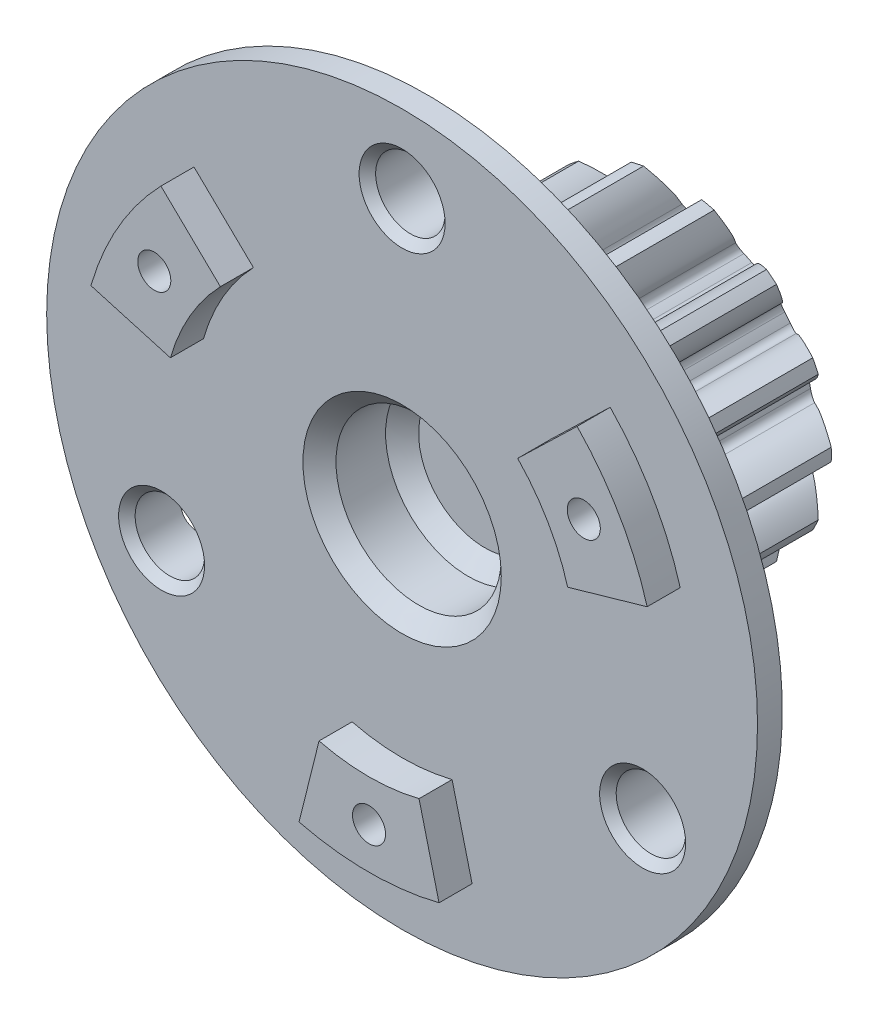
SolidWorks part; units mm, degrees
ref_plane "Front Plane" through (0, 0, 0) normal (0, 0, 1) x (1, 0, 0)
ref_plane "Top Plane" through (0, 0, 0) normal (0, 1, 0) x (1, 0, 0)
ref_plane "Right Plane" through (0, 0, 0) normal (1, 0, 0) x (0, 0, -1)
ref_axis "Axis1" through (0, 0, -88.99) along (0, 0, 1)
sketch "Sketch1" plane through (0, 0, 0) normal (0, 0, 1) x (1, 0, 0)
  circle A0 centre (0, 0) radius 9.6
extrude "LaShenA" add sketch "Sketch1" along normal blind 15
sketch "SketchA" plane through (0, 0, 15) normal (0, 0, 1) x (1, 0, 0)
  line L0 (0, 0) -> (0, 9.6) construction
  arc A0 (0.2639, 6.895) -> (-0.2639, 6.895) centre (0, 0) ccw
  arc A1 (2.4844, 10.0489) -> (-2.4844, 10.0489) centre (0, 0) ccw
  arc A2 (-0.2639, 6.895) -> (-0.7348, 7.3025) centre (-0.2814, 7.3506) cw
  arc A3 (0.7348, 7.3025) -> (0.2639, 6.895) centre (0.2814, 7.3506) cw
  circle A4 centre (0, 0) radius 7.8934 construction
  circle A5 centre (0, 0) radius 9.6 construction
  circle A6 centre (0, 0) radius 6.9 construction
  circle A7 centre (0, 0) radius 8.4 construction
  spline S0 degree 3 poles (0.7348, 7.3025) (0.7544, 7.4871) (0.7376, 7.7039) (0.7817, 7.9284) (0.7974, 7.9855) (0.8111, 8.0306) (0.8285, 8.0821) (0.85, 8.1398) (0.8759, 8.2036) (0.9067, 8.2732) (0.9427, 8.3484) (0.9843, 8.4289) (1.0318, 8.5144) (1.0856, 8.6047) (1.146, 8.6994) (1.2133, 8.7982) (1.2878, 8.9008) (1.3699, 9.0069) (1.4597, 9.116) (1.5576, 9.2278) (1.6637, 9.3419) (1.7784, 9.4579) (1.9017, 9.5753) (2.034, 9.6938) (2.2261, 9.8557) (2.3786, 9.9726) (2.4844, 10.0489) knots 0.117633 0.117633 0.117633 0.117633 0.26174 0.285267 0.295626 0.307868 0.321993 0.338001 0.355893 0.375668 0.397327 0.420869 0.446294 0.473603 0.502795 0.53387 0.566829 0.601671 0.638396 0.677005 0.717497 0.759872 0.804131 0.850273 0.898299 1 1 1 1
  spline S1 degree 3 poles (-0.7348, 7.3025) (-0.7544, 7.4871) (-0.7376, 7.7039) (-0.7817, 7.9284) (-0.7974, 7.9855) (-0.8111, 8.0306) (-0.8285, 8.0821) (-0.85, 8.1398) (-0.8759, 8.2036) (-0.9067, 8.2732) (-0.9427, 8.3484) (-0.9843, 8.4289) (-1.0318, 8.5144) (-1.0856, 8.6047) (-1.146, 8.6994) (-1.2133, 8.7982) (-1.2878, 8.9008) (-1.3699, 9.0069) (-1.4597, 9.116) (-1.5576, 9.2278) (-1.6637, 9.3419) (-1.7784, 9.4579) (-1.9017, 9.5753) (-2.034, 9.6938) (-2.2261, 9.8557) (-2.3786, 9.9726) (-2.4844, 10.0489) knots 0.117633 0.117633 0.117633 0.117633 0.26174 0.285267 0.295626 0.307868 0.321993 0.338001 0.355893 0.375668 0.397327 0.420869 0.446294 0.473603 0.502795 0.53387 0.566829 0.601671 0.638396 0.677005 0.717497 0.759872 0.804131 0.850273 0.898299 1 1 1 1
  dimension "D1" = 0.456
  dimension "Db" = 15.7868
  dimension "Da" = 19.2
  dimension "Df" = 13.8
  dimension "Dn" = 16.8
extrude "Cut-ExtrudeA" cut sketch "SketchA" against normal blind 15
pattern_circular "www.KYTool.cn" count 14 over 360 about axis through (0, 0, -88.99) along (0, 0, 1) of "Cut-ExtrudeA"
sketch "Sketch3" plane through (0, 0, 15) normal (0, 0, 1) x (1, 0, 0)
  circle A0 centre (0, 0) radius 21.5
  dimension "D1" = 43
extrude "Boss-Extrude2" add sketch "Sketch3" along normal blind 3.5
sketch "Sketch4" plane through (0, 0, 15) normal (0, 0, -1) x (-1, 0, 0)
  circle A0 centre (0, 0) radius 15 construction
  circle A1 centre (0, 0) radius 16.8 construction
  circle A2 centre (0, 16.8) radius 2.1
  dimension "D1" = 30
  dimension "D2" = 33.6
  dimension "D3" = 4.2
extrude "Cut-Extrude2" cut sketch "Sketch4" against normal through all
chamfer "Chamfer1" distance 0.5 angle 45 1 edges at (-2.1, 16.8, 18.5)
pattern_circular "CirPattern2" count 3 over 360 about axis through (0, 0, 15) along (0, 0, 1) of "Chamfer1", "Cut-Extrude2"
sketch "Sketch5" plane through (0, 0, 15) normal (0, 0, -1) x (-1, 0, 0)
  circle A0 centre (0, 0) radius 19.5
  circle A1 centre (0, 0) radius 21.5
  circle A2 centre (0, 0) radius 21.5
  dimension "D2" = 39
  dimension "D1" = 0
extrude "Cut-Extrude3" cut sketch "Sketch5" against normal blind 2
sketch "Sketch6" plane through (0, 0, 18.5) normal (0, 0, 1) x (1, 0, 0)
  line L0 (-4.2336, -16.9802) -> (0, 0)
  line L1 (0, 0) -> (4.2336, -16.9802)
  line L2 (0, 0) -> (0, -32.1577) construction
  arc A0 (-3.024, -12.1287) -> (3.024, -12.1287) centre (0, 0) ccw
  circle A1 centre (0, 0) radius 21.5
  circle A2 centre (0, 0) radius 21.5
  arc A3 (-4.2336, -16.9802) -> (4.2336, -16.9802) centre (0, 0) ccw
  dimension "D2" = 12.5
  dimension "D3" = 17.5
  dimension "D4" = 14
  dimension "D5" = 14
  dimension "D1" = 0
extrude "Boss-Extrude3" add sketch "Sketch6" along normal blind 2 contours A0 L2 A3 L1 | L2 A0 L0 A3 region at (-1.8404, -14.9887, 18.5) region at (1.8404, -14.9887, 18.5)
sketch "Sketch7" plane through (0, 0, 20.5) normal (0, 0, 1) x (1, 0, 0)
  line L0 (0, 0) -> (0, -24.1997) construction
  circle A0 centre (0, 0) radius 15
  circle A1 centre (0, -15) radius 1
  dimension "D1" = 30
  dimension "D2" = 2
extrude "Cut-Extrude4" cut sketch "Sketch7" against normal through all contours A0 L0 A1 | A1 L0 A0 | L0 A1 A0 | L0 A0 A1 region at (0.4197, -14.5696, 20.5) region at (-0.4197, -14.5696, 20.5) region at (0.429, -15.4184, 20.5) region at (-0.429, -15.4184, 20.5)
pattern_circular "CirPattern3" count 3 over 360 about axis through (0, 0, 18.5) along (0, 0, 1) of "Cut-Extrude4", "Boss-Extrude3"
chamfer "Chamfer2" distance 1 angle 45 3 edges at (13.9904, 7.5, 15) (-11.9904, 7.5, 15) (1, -15, 15)
sketch "Sketch8" plane through (0, 0, 0) normal (0, 1, 0) x (1, 0, 0)
  line L0 (-9.6, 0) -> (-9.6, -2.1362)
  line L1 (-9.6, -2.1362) -> (-5.9, 0)
  line L2 (-5.9, 0) -> (-9.6, 0)
  line L3 (-6.1674, 0) -> (-8.4752, 0) construction
  line L4 (0, 0) -> (0, 4.6418) construction
  dimension "D1" = 30
  dimension "D2" = 3.7
  dimension "D3" = 9.6
revolve "Cut-Revolve1" cut sketch "Sketch8" angle 360 about L4
sketch "Sketch9" plane through (0, 0, 18.5) normal (0, 0, 1) x (1, 0, 0)
  circle A0 centre (0, 0) radius 5
  dimension "D1" = 10
extrude "Cut-Extrude5" cut sketch "Sketch9" against normal blind 5
chamfer "Chamfer3" distance 1 angle 45 2 edges at (5, 0, 13.5) (5, 0, 18.5)
chamfer "Chamfer4" distance 1 angle 45 1 edges at (-19.5, 0, 15)
